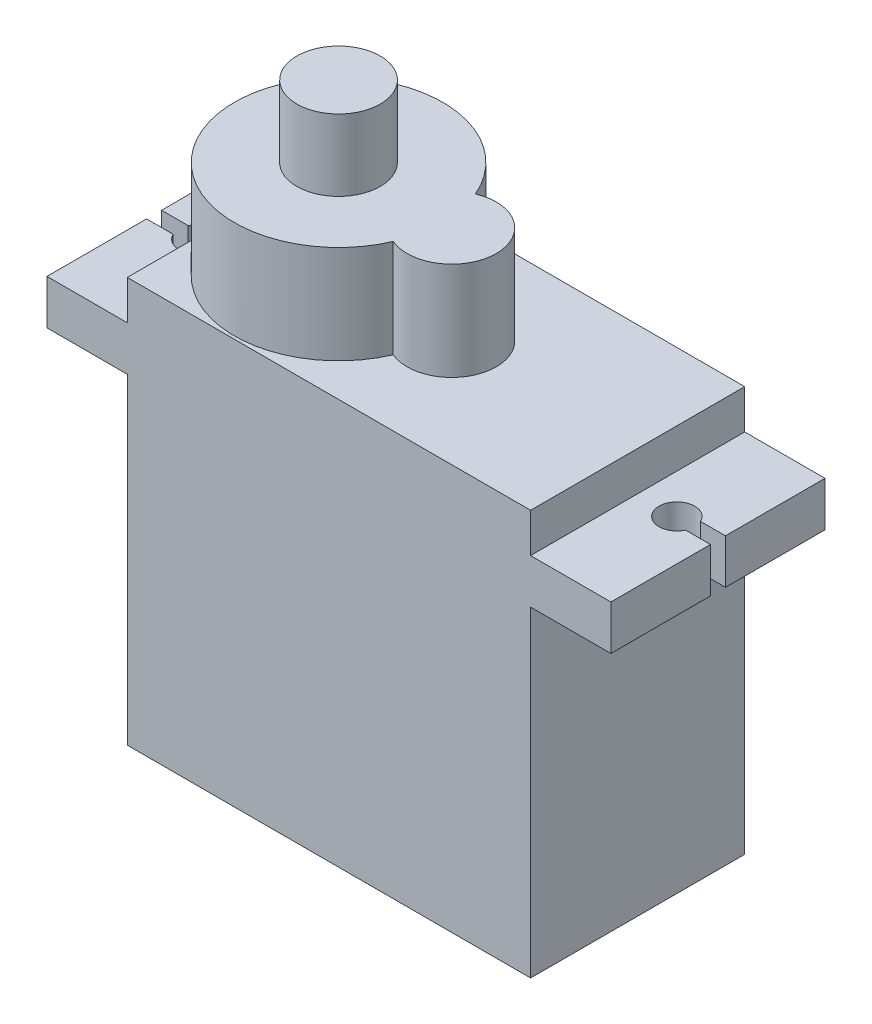
SolidWorks part; units mm, degrees
ref_plane "Front Plane" through (0, 0, 0) normal (0, 0, 1) x (1, 0, 0)
ref_plane "Top Plane" through (0, 0, 0) normal (0, 1, 0) x (1, 0, 0)
ref_plane "Right Plane" through (0, 0, 0) normal (1, 0, 0) x (0, 0, -1)
sketch "Sketch1" plane through (0, 0, 0) normal (0, 1, 0) x (1, 0, 0)
  line L1 (-46.1955, 4.7431) -> (-23.5955, 4.7431)
  line L2 (-46.1955, 4.7431) -> (-46.1955, -7.2569)
  line L3 (-46.1955, -7.2569) -> (-23.5955, -7.2569)
  line L4 (-23.5955, 4.7431) -> (-23.5955, -7.2569)
  dimension "D1" = 22.6
  dimension "D2" = 12
extrude "Boss-Extrude1" add sketch "Sketch1" along normal blind 22.7
ref_plane "Plane1" through (-23.5955, 22.7, -4.7431) normal (0, -1, 0) x (1, 0, 0)
sketch "Sketch2" plane through (-23.5955, 22.7, -4.7431) normal (0, -1, 0) x (1, 0, 0)
ref_plane "Plane2" through (-46.1955, 22.7, -4.7431) normal (0, 0, 1) x (1, 0, 0)
sketch "Sketch3" plane through (-46.1955, 22.7, -4.7431) normal (0, 0, 1) x (1, 0, 0)
sketch "Sketch4" plane through (0, 22.7, 0) normal (0, 1, 0) x (-1, 0, 0)
  line L0 (46.1955, 1.2569) -> (40.3555, 1.2569)
  line L1 (46.1955, -4.7431) -> (46.1955, 7.2569) construction
  circle A0 centre (40.3555, 1.2569) radius 5.84
extrude "Boss-Extrude6" add sketch "Sketch4" along normal blind 5.5 contours A0 region at (-34.6807, 22.7, 1.2569)
sketch "Sketch12" plane through (0, 28.2, 0) normal (0, 1, 0) x (-1, 0, 0)
  circle A0 centre (40.3555, 1.2569) radius 2.335
extrude "Boss-Extrude7" add sketch "Sketch12" along normal blind 4
sketch "Sketch13" plane through (0, 22.7, 0) normal (0, 1, 0) x (-1, 0, 0)
  line L0 (34.5155, 1.2569) -> (34.0155, 1.2569)
  circle A0 centre (40.3555, 1.2569) radius 5.84 construction
  circle A1 centre (34.0155, 1.2569) radius 2.5
  circle M2 centre (40.3555, 1.2569) radius 5.84
extrude "Boss-Extrude8" add sketch "Sketch13" along normal blind 5.5 contours A1 M2 region at (-33.3061, 22.7, 1.2569)
sketch "Sketch14" plane through (-23.5955, 0, 0) normal (1, 0, 0) x (0, 0, -1)
  line L0 (-7.2569, 22.7) -> (-7.2569, 20.5)
  line L1 (-7.2569, 22.7) -> (-7.2569, 0) construction
  line L2 (4.7431, 22.7) -> (4.7431, 0) construction
  line L3 (-7.2569, 20.5) -> (4.7431, 20.5)
  line L4 (-7.2569, 20.5) -> (-7.2569, 18)
  line L5 (-7.2569, 18) -> (4.7431, 18)
  line L6 (4.7431, 20.5) -> (4.7431, 18)
  line L7 (-7.2569, 0) -> (4.7431, 0) construction
  line L8 (-7.2569, 22.7) -> (4.7431, 22.7) construction
  line M2 (4.7431, 0) -> (4.7431, 22.7)
  line M4 (-7.2569, 22.7) -> (-7.2569, 0)
  dimension "D3" = 2.2
  dimension "boss_height" = 18
  dimension "boss_thickness" = 2.5
extrude "Boss-Extrude10" add sketch "Sketch14" along normal blind 4.5 contours L5 L3 M4 M2 region at (-23.5955, 19.25, 1.2569)
sketch "Sketch15" plane through (0, 20.5, 0) normal (0, 1, 0) x (-1, 0, 0)
  line L0 (19.0955, 7.2569) -> (19.0955, -4.7431) construction
  line L1 (19.0955, 1.2569) -> (20.5955, 1.2569)
  line L2 (19.0955, 1.6769) -> (19.0955, 0.8369)
  line L3 (19.0955, 0.8369) -> (20.5955, 0.8369)
  line L4 (50.6955, 1.2569) -> (48.3955, 1.2569)
  line L5 (20.5955, 1.6769) -> (20.5955, 0.8369)
  line L6 (19.0955, 1.6769) -> (20.5955, 1.6769)
  line L7 (19.0955, 1.2569) -> (21.3955, 1.2569)
  circle A0 centre (21.3955, 1.2569) radius 1
  circle A1 centre (48.3955, 1.2569) radius 1
  line M3 (19.0955, 7.2569) -> (19.0955, -4.7431)
extrude "Cut-Extrude3" cut sketch "Sketch15" along direction (0, 1, 0) on the side against the normal through all contours L3 A0 L6 L5 | L6 A0 L7 L5 | L7 A0 L3 L5 | A0 L6 L1 M3 | A0 L1 L3 M3 region at (-19.7609, 20.5, 1.4693) region at (-19.7609, 20.5, 1.0445) region at (-20.5084, 20.5, 1.448) region at (-20.5084, 20.5, 1.0657) region at (-21.4377, 20.5, 1.2569)
sketch "Sketch16" plane through (-46.1955, 0, 0) normal (-1, 0, 0) x (0, 0, 1)
  line L0 (7.2569, 24.5) -> (7.2569, 20.5)
  line L1 (7.2569, 22.7) -> (7.2569, 0) construction
  line L2 (7.2569, 20.5) -> (7.2569, 18)
  line L3 (7.2569, 20.5) -> (-4.7431, 20.5)
  line L4 (-4.7431, 22.7) -> (-4.7431, 0) construction
  line L5 (7.2569, 18) -> (-4.7431, 18)
  line L6 (-4.7431, 0) -> (7.2569, 0) construction
  line L7 (-4.7431, 22.7) -> (1.2569, 22.7) construction
  line M2 (7.2569, 0) -> (7.2569, 22.7)
  line M5 (-4.7431, 22.7) -> (-4.7431, 0)
  dimension "D3" = 2.2
  dimension "boss_height" = 18
  dimension "boss_thickness" = 2.5
extrude "Boss-Extrude11" add sketch "Sketch16" along normal blind 4.5 contours L5 L3 M2 M5 region at (-46.1955, 19.25, 1.2569)
sketch "Sketch17" plane through (0, 20.5, 0) normal (0, 1, 0) x (-1, 0, 0)
  line L0 (50.6955, 0.8369) -> (50.6955, 1.6769)
  line L1 (50.6955, 1.2569) -> (49.1955, 1.2569)
  line L2 (50.6955, 1.6769) -> (49.1955, 1.6769)
  line L3 (49.1955, 0.8369) -> (49.1955, 1.6769)
  line L4 (50.6955, 7.2569) -> (50.6955, -4.7431) construction
  line L5 (50.6955, 0.8369) -> (49.1955, 0.8369)
  line L6 (50.6955, 1.2569) -> (48.2955, 1.2569)
  circle A0 centre (48.2955, 1.2569) radius 1
  line M3 (50.6955, -4.7431) -> (50.6955, 7.2569)
extrude "Cut-Extrude4" cut sketch "Sketch17" along direction (0, -1, 0) on the side against the normal through all contours L3 A0 | A0 L3 L5 L1 M3 | L3 A0 L6 | L6 A0 L3 | A0 L1 L0 L2 L3 region at (-49.9802, 20.5, 1.0446) region at (-49.9802, 20.5, 1.4691) region at (-48.2777, 20.5, 1.2569) region at (-49.2358, 20.5, 1.0928) region at (-49.2358, 20.5, 1.4209)
